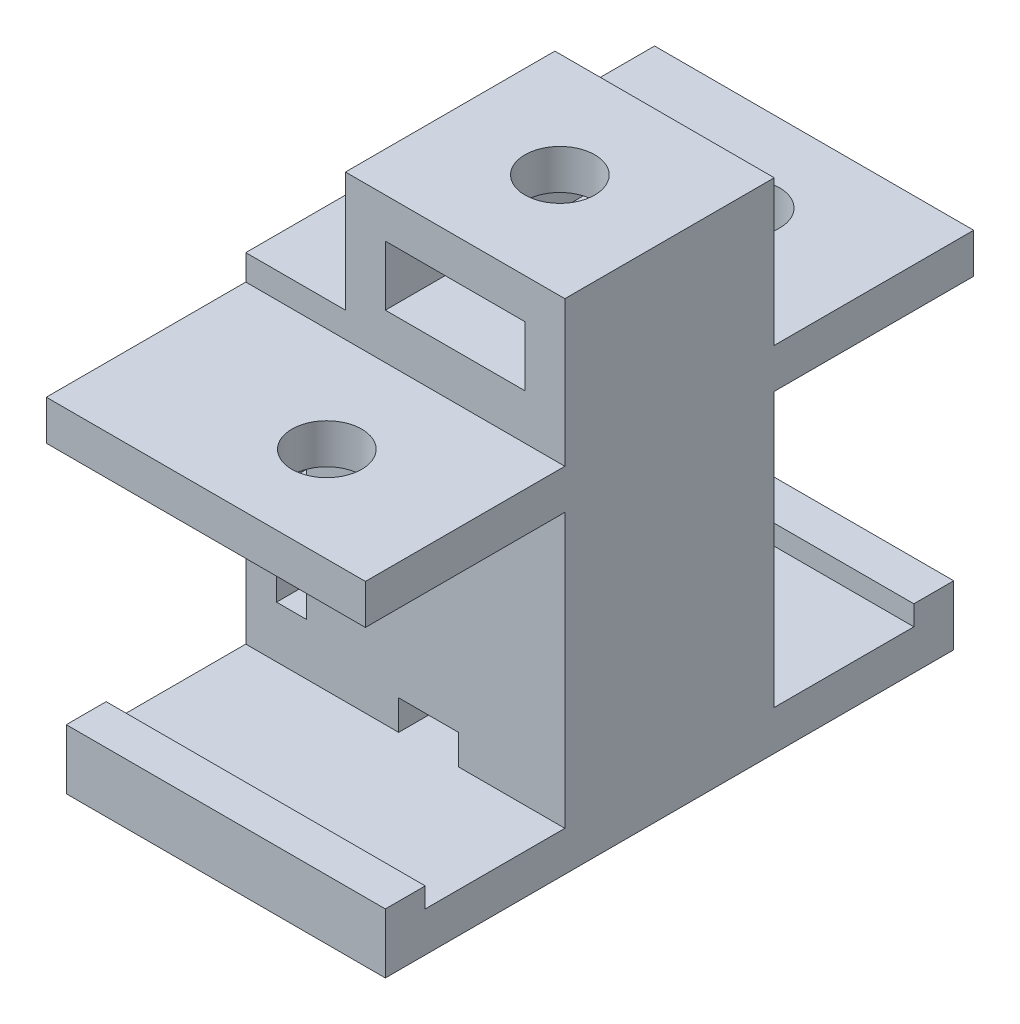
SolidWorks part; units mm, degrees
ref_plane "Front Plane" through (0, 0, 0) normal (0, 0, 1) x (1, 0, 0)
ref_plane "Top Plane" through (0, 0, 0) normal (0, 1, 0) x (1, 0, 0)
ref_plane "Right Plane" through (0, 0, 0) normal (1, 0, 0) x (0, 0, -1)
sketch "Sketch1" plane through (0, 0, 0) normal (0, 1, 0) x (1, 0, 0)
  line L9 (0, 0) -> (16, 0)
  line L10 (0, 0) -> (0, 10.5)
  line L11 (0, 10.5) -> (16, 10.5)
  line L12 (16, 0) -> (16, 10.5)
  dimension "D1" = 16
  dimension "D2" = 10.5
extrude "Boss-Extrude1" add sketch "Sketch1" along normal blind 25
sketch "Sketch3" plane through (0, 0, 0) normal (0, 0, 1) x (1, 0, 0)
  line L0 (16, 25) -> (16, 0) construction
  line L1 (0, 0) -> (16, 0)
  line L2 (0, 0) -> (0, 2)
  line L3 (0, 2) -> (16, 2)
  line L4 (16, 0) -> (16, 2)
  line L5 (0, 25) -> (0, 0) construction
  line L6 (0, 15.7217) -> (16, 15.7217)
  line L7 (0, 15.7217) -> (0, 17.7217)
  line L8 (0, 17.7217) -> (16, 17.7217)
  line L9 (16, 15.7217) -> (16, 17.7217)
  dimension "D1" = 2
  dimension "D2" = 2
extrude "Boss-Extrude2" add sketch "Sketch3" along normal blind 7
extrude "Boss-Extrude5" add sketch "Sketch3<2>" against normal blind 7 from surface starting at face at (8, 12.5, -10.5)
sketch "Sketch3<2>" plane through (0, 0, 0) normal (0, 0, 1) x (1, 0, 0) same geometry as "Sketch3"
sketch "Sketch2" plane through (0, 0, 0) normal (0, 0, 1) x (1, 0, 0)
  line L0 (7.6681, 2) -> (10.6681, 2)
  line L3 (7.6279, 13.8034) -> (10.6279, 13.8034)
  line L8 (7.6279, 13.8034) -> (7.6279, 15.3034)
  line L9 (7.6279, 15.3034) -> (10.6279, 15.3034)
  line L14 (10.6279, 13.8034) -> (10.6279, 15.3034)
  line L15 (7.6681, 3.5) -> (10.6681, 3.5)
  line L16 (7.6681, 2) -> (7.6681, 3.5)
  line L21 (10.6681, 2) -> (10.6681, 3.5)
  line L22 (1.5449, 6.5926) -> (1.5449, 4.5926)
  line L23 (1.5449, 11.6062) -> (3.0449, 11.6062)
  line L24 (1.5449, 11.6062) -> (1.5449, 9.6062)
  line L25 (1.5449, 9.6062) -> (3.0449, 9.6062)
  line L26 (3.0449, 11.6062) -> (3.0449, 9.6062)
  line L27 (1.5449, 4.5926) -> (3.0449, 4.5926)
  line L28 (3.0449, 6.5926) -> (3.0449, 4.5926)
  line L29 (1.5449, 6.5926) -> (3.0449, 6.5926)
  dimension "D1" = 1.5
  dimension "D2" = 3
  dimension "D3" = 1.5
  dimension "D4" = 3
  dimension "D5" = 1.5
  dimension "D6" = 2
  dimension "D7" = 1.5
extrude "Cut-Extrude1" cut sketch "Sketch2" against normal blind 20
sketch "Sketch5" plane through (0, 0, 7) normal (0, 0, 1) x (1, 0, 0)
  line L4 (0, 17.7217) -> (0, 15.7217)
  line L5 (0, 15.7217) -> (16, 15.7217)
  line L6 (16, 15.7217) -> (16, 17.7217)
  line L7 (16, 17.7217) -> (0, 17.7217)
  line L8 (0, 17.7217) -> (0, 15.7217)
  line L9 (0, 15.7217) -> (16, 15.7217)
  line L10 (16, 15.7217) -> (16, 17.7217)
  line L11 (16, 17.7217) -> (0, 17.7217)
  dimension "D1" = 0
extrude "Boss-Extrude3" add sketch "Sketch5" along normal blind 3
extrude "Boss-Extrude6" add sketch "Sketch5<2>" against normal blind 3 from surface starting at face at (8, 16.7217, -17.5)
sketch "Sketch5<2>" plane through (0, 0, 7) normal (0, 0, 1) x (1, 0, 0) same geometry as "Sketch5"
sketch "Sketch4" plane through (0, 17.7217, 0) normal (0, 1, 0) x (1, 0, 0)
  line L0 (16, 5.25) -> (0, 5.25) construction
  line L1 (16, 0) -> (16, 10.5) construction
  line L2 (0, 10.5) -> (0, 0) construction
  circle A0 centre (9.2913, -5.2271) radius 1.75
  circle A1 centre (9.2913, 15.7271) radius 1.75
  dimension "D1" = 3.5
extrude "Cut-Extrude2" cut sketch "Sketch4" against normal blind 10
sketch "Sketch6" plane through (0, 0, 7) normal (0, 0, 1) x (1, 0, 0)
  line L0 (16, 15.7217) -> (16, 2) construction
  line L1 (0, 0) -> (16, 0)
  line L2 (0, 0) -> (0, 3)
  line L3 (0, 3) -> (16, 3)
  line L4 (16, 0) -> (16, 3)
  dimension "D1" = 3
extrude "Boss-Extrude4" add sketch "Sketch6" along normal blind 2
extrude "Boss-Extrude7" add sketch "Sketch6<2>" against normal blind 2 from surface starting at face at (8, 1, -17.5)
sketch "Sketch6<2>" plane through (0, 0, 7) normal (0, 0, 1) x (1, 0, 0) same geometry as "Sketch6"
sketch "Sketch7" plane through (0, 0, 0) normal (-1, 0, 0) x (0, 0, 1)
  line L0 (0, 25) -> (0, 17.7217) construction
  line L1 (-10.5, 25) -> (0, 25)
  line L2 (-10.5, 25) -> (-10.5, 19)
  line L3 (-10.5, 19) -> (0, 19)
  line L4 (0, 25) -> (0, 19)
  dimension "D1" = 6
extrude "Cut-Extrude3" cut sketch "Sketch7" against normal blind 5
sketch "Sketch8" plane through (0, 25, 0) normal (0, 1, 0) x (1, 0, 0)
  line L0 (5, 0) -> (16, 10.5) construction
  circle A0 centre (10.5, 5.25) radius 1.75
  dimension "D1" = 3.5
extrude "Cut-Extrude4" cut sketch "Sketch8" against normal blind 5
sketch "Sketch10" plane through (0, 0, 0) normal (0, 0, 1) x (1, 0, 0)
  line L0 (10.5, 25) -> (10.5, 19.0711) construction
  line L1 (5, 25) -> (16, 25) construction
  line L3 (7, 20) -> (14, 20)
  line L4 (7, 20) -> (7, 23)
  line L5 (7, 23) -> (14, 23)
  line L6 (14, 20) -> (14, 23)
  dimension "D1" = 3
  dimension "D2" = 7
  dimension "D3" = 3.5
  dimension "D4" = 5
extrude "Cut-Extrude5" cut sketch "Sketch10" against normal blind 15
